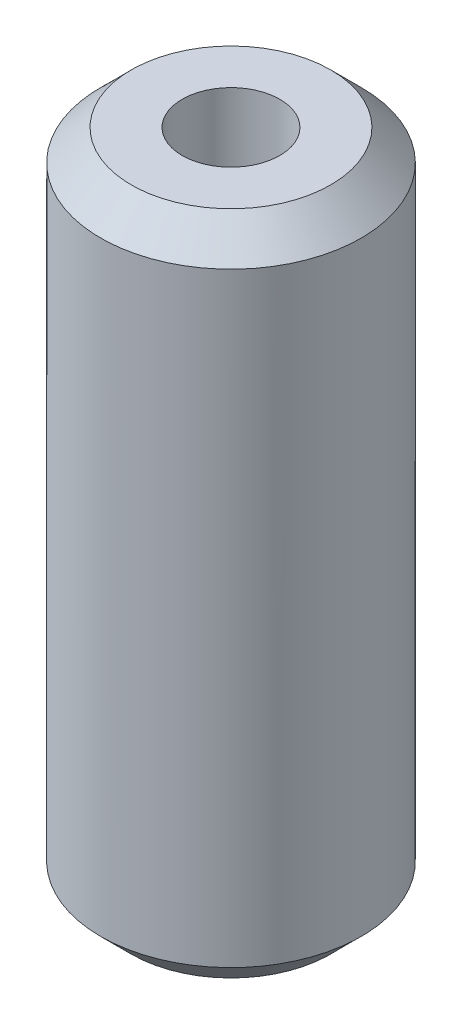
SolidWorks part; units mm, degrees
ref_plane "Front Plane" through (0, 0, 0) normal (0, 0, 1) x (1, 0, 0)
ref_plane "Top Plane" through (0, 0, 0) normal (0, 1, 0) x (1, 0, 0)
ref_plane "Right Plane" through (0, 0, 0) normal (1, 0, 0) x (0, 0, -1)
sketch "Sketch1" plane through (0, 0, 0) normal (0, 1, 0) x (1, 0, 0)
  circle A0 centre (0, 0) radius 25
  dimension "SHAFT_OD" = 50
extrude "Boss-Extrude1" add sketch "Sketch1" along normal blind 127.7594
sketch "Sketch2" plane through (0, 0, 0) normal (0, 1, 0) x (1, 0, 0)
  circle A0 centre (0, 0) radius 9.3554
  dimension "BORE_D" = 18.7109
extrude "Cut-Extrude1" cut sketch "Sketch2" along normal through all
chamfer "Chamfer1" distance 5.8806 angle 45 2 edges at (0, 127.7594, 25) (0, 0, 25)
